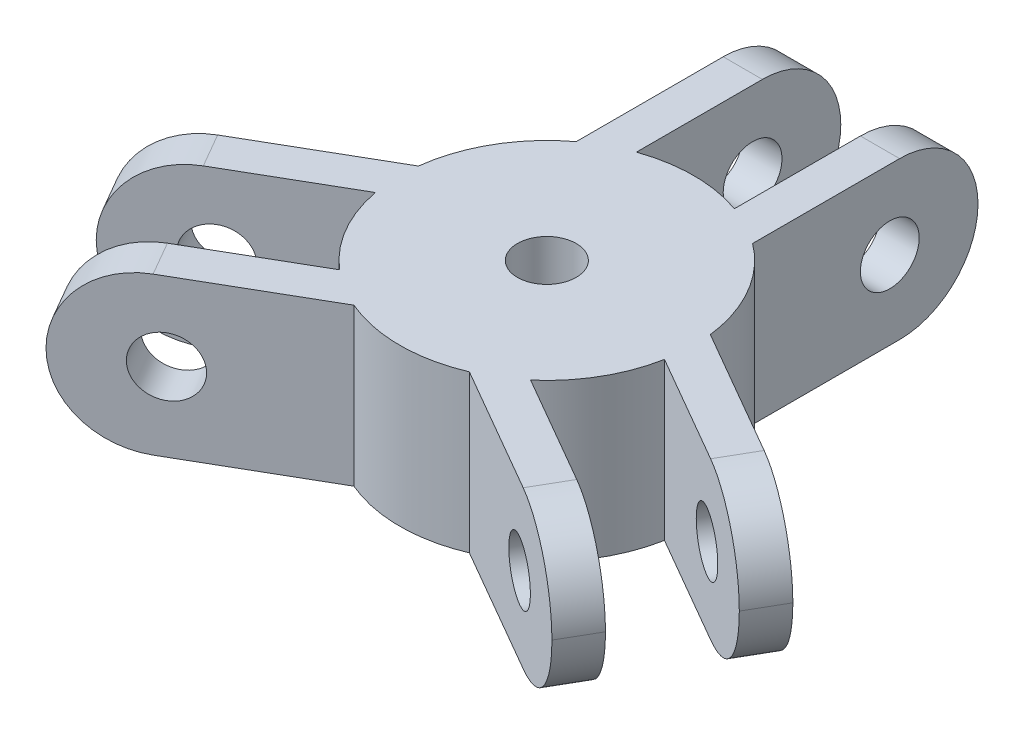
SolidWorks part; units mm, degrees
ref_plane "Front Plane" through (0, 0, 0) normal (0, 0, 1) x (1, 0, 0)
ref_plane "Top Plane" through (0, 0, 0) normal (0, 1, 0) x (1, 0, 0)
ref_plane "Right Plane" through (0, 0, 0) normal (1, 0, 0) x (0, 0, -1)
sketch "Sketch1" plane through (0, 0, 0) normal (0, 1, 0) x (1, 0, 0)
  line L0 (0, 0) -> (0, 17.5) construction
  line L4 (0, 0) -> (-15.1554, -8.75) construction
  line L5 (0, 0) -> (15.1554, -8.75) construction
  line L6 (-4.5, 0) -> (-4.5, 17.5)
  line L7 (-4.5, 0) -> (4.5, 0)
  line L8 (-4.5, 17.5) -> (4.5, 17.5)
  line L9 (4.5, 0) -> (4.5, 17.5)
  line L10 (0, 17.5) -> (0, 0) construction
  line L11 (-4.5, 8.75) -> (4.5, 8.75) construction
  line L16 (2.25, -3.8971) -> (-12.9054, -12.6471)
  line L17 (2.25, -3.8971) -> (-2.25, 3.8971)
  line L18 (2.25, 3.8971) -> (17.4054, -4.8529)
  line L19 (2.25, 3.8971) -> (-2.25, -3.8971)
  line L20 (17.4054, -4.8529) -> (12.9054, -12.6471)
  line L21 (-2.25, -3.8971) -> (12.9054, -12.6471)
  line L22 (15.1554, -8.75) -> (0, 0) construction
  line L23 (9.8277, -0.4779) -> (5.3277, -8.2721) construction
  line L24 (-12.9054, -12.6471) -> (-17.4054, -4.8529)
  line L25 (-2.25, 3.8971) -> (-17.4054, -4.8529)
  line L26 (-15.1554, -8.75) -> (0, 0) construction
  line L27 (-5.3277, -8.2721) -> (-9.8277, -0.4779) construction
  line L28 (1.25, -2.1651) -> (-13.9054, -10.9151)
  line L29 (1.25, -2.1651) -> (-1.25, 2.1651)
  line L30 (-13.9054, -10.9151) -> (-16.4054, -6.5849)
  line L31 (-1.25, 2.1651) -> (-16.4054, -6.5849)
  line L32 (-15.1554, -8.75) -> (0, 0) construction
  line L33 (-6.3277, -6.5401) -> (-8.8277, -2.2099) construction
  line L34 (-2.5, 0) -> (-2.5, 17.5)
  line L35 (-2.5, 0) -> (2.5, 0)
  line L36 (-2.5, 17.5) -> (2.5, 17.5)
  line L37 (2.5, 0) -> (2.5, 17.5)
  line L38 (0, 17.5) -> (0, 0) construction
  line L39 (-2.5, 8.75) -> (2.5, 8.75) construction
  line L40 (-1.25, -2.1651) -> (13.9054, -10.9151)
  line L41 (-1.25, -2.1651) -> (1.25, 2.1651)
  line L42 (13.9054, -10.9151) -> (16.4054, -6.5849)
  line L43 (1.25, 2.1651) -> (16.4054, -6.5849)
  line L44 (15.1554, -8.75) -> (0, 0) construction
  line L45 (6.3277, -6.5401) -> (8.8277, -2.2099) construction
  circle A1 centre (0, 0) radius 7.5
  point P5 (0, 8.75)
  point P6 (0, 8.75)
  point P7 (-7.5777, -4.375)
  point P11 (7.5777, -4.375)
  point P12 (-7.5777, -4.375)
  point P17 (7.5777, -4.375)
  dimension "D1" = 17.5
  dimension "D6" = 15
  dimension "D2" = 120
  dimension "D3" = 120
  dimension "D4" = 9
  dimension "D5" = 5
extrude "Boss-Extrude1" add sketch "Sketch1" along normal blind 8 contours L28 A1 L16 L21 L19 | A1 L28 L24 L16 | A1 L25 L24 L31 | L25 A1 L31 L7 L6 | L31 L34 L17 L25 L6 L7 | L40 L28 L19 L21 L16 L17 | L31 A1 L28 L19 L7 | L7 L34 L31 | L34 L7 L17 L31 | L34 L31 L17 | L40 L19 L28 | L19 L40 L28 L17 | L28 L40 L17 | L6 A1 L25 | L16 A1 L21 | L21 A1 L40 L17 L16 | L40 A1 L43 L7 L17 | L43 L37 L7 | L43 L19 L7 L37 | L37 A1 L34 L17 L19 | L37 L43 L7 L9 L18 L19 | L19 L43 L37 | L34 A1 L6 L25 L17 | L9 A1 L37 L19 L18 | L18 A1 L9 | L43 A1 L18 L9 L7 | A1 L43 L20 L18 | A1 L21 L20 L40 | A1 L9 L8 L37 | A1 L34 L8 L6 region at (-3.992, 0, 2.3048) region at (-3.2778, 0, -0.4972) region at (-5.9834, 0, -0.592) region at (-3.5, 0, -2.0207) region at (-1.4583, 0, -0.842) region at (-5.7082, 0, -3.2956) region at (-3.5044, 0, -4.8858) region at (-2.0694, 0, -2.5901) region at (-12.1903, 0, 2.9778) region at (1.4583, 0, -0.842) region at (3.992, 0, 2.3048) region at (0, 0, -4.6096) region at (0, 0, 1.6839) region at (-3.5163, 0, -12.0461) region at (-8.6741, 0, 9.0682) region at (-2.4791, 0, 5.4778) region at (3.2778, 0, -0.4972) region at (1.2083, 0, 3.0872) region at (2.0694, 0, -2.5901) region at (-1.2083, 0, 3.0872) region at (0, 0, 4.0415) region at (0, 0, 6.5912) region at (3.5, 0, -2.0207) region at (3.5044, 0, -4.8858) region at (3.5163, 0, -12.0461) region at (2.4791, 0, 5.4778) region at (8.6741, 0, 9.0682) region at (5.9834, 0, -0.592) region at (5.7082, 0, -3.2956) region at (12.1903, 0, 2.9778)
sketch "Sketch2" plane through (2.25, 0, 3.8971) normal (0.5, 0, 0.866) x (0.866, 0, -0.5)
  line L0 (-17.5, 4) -> (-6, 4) construction
  line L1 (-17.5, 8) -> (-17.5, 0) construction
  line L2 (-6, 8) -> (-6, 0) construction
  circle A0 centre (-13, 4) radius 1.5
  dimension "D1" = 3
  dimension "D2" = 4.5
extrude "Cut-Extrude1" cut sketch "Sketch2" against normal up to surface (9 mm away) up to face at (-12.4258, 4, 1.9779)
sketch "Sketch3" plane through (-4.5, 0, 0) normal (-1, 0, 0) x (0, 0, 1)
  line L0 (-17.5, 4) -> (-6, 4) construction
  line L1 (-17.5, 8) -> (-17.5, 0) construction
  line L2 (-6, 8) -> (-6, 0) construction
  circle A0 centre (-13, 4) radius 1.5
  dimension "D1" = 3
  dimension "D2" = 4.5
sketch "Sketch4" plane through (2.25, 0, -3.8971) normal (0.5, 0, -0.866) x (-0.866, 0, -0.5)
  line L0 (-17.5, 4) -> (-6, 4) construction
  line L1 (-17.5, 8) -> (-17.5, 0) construction
  line L2 (-6, 8) -> (-6, 0) construction
  circle A0 centre (-13, 4) radius 1.5
  dimension "D1" = 3
  dimension "D2" = 4.5
extrude "Cut-Extrude2" cut sketch "Sketch3" against normal up to surface (9 mm away) up to face at (4.5, 4, -11.75)
extrude "Cut-Extrude3" cut sketch "Sketch4" against normal up to surface (9 mm away) up to face at (7.9258, 4, 9.7721)
sketch "Sketch5" plane through (0, 0, 0) normal (0, -1, 0) x (1, 0, 0)
  circle A0 centre (0, 0) radius 4.5
  arc A1 (2.9462, 6.8971) -> (-2.9462, 6.8971) centre (0, 0) ccw construction
  dimension "D1" = 3
extrude "Cut-Extrude4" cut sketch "Sketch5" against normal offset from surface (5 mm away) 3 up to face at (0, 8, 0)
sketch "Sketch6" plane through (0, 5, 0) normal (0, -1, 0) x (1, 0, 0)
  circle A0 centre (0, 0) radius 1.5
  dimension "D1" = 3
extrude "Cut-Extrude5" cut sketch "Sketch6" against normal through all
fillet "Fillet1" radius 4 12 edges at (-13.4054, 0, 11.7811) (-16.9054, 0, 5.7189) (-3.5, 0, -17.5) (3.5, 0, -17.5) (3.5, 8, -17.5) (-3.5, 8, -17.5) (-16.9054, 8, 5.7189) (-13.4054, 8, 11.7811) (13.4054, 8, 11.7811) (13.4054, 0, 11.7811) (16.9054, 0, 5.7189) (16.9054, 8, 5.7189)
